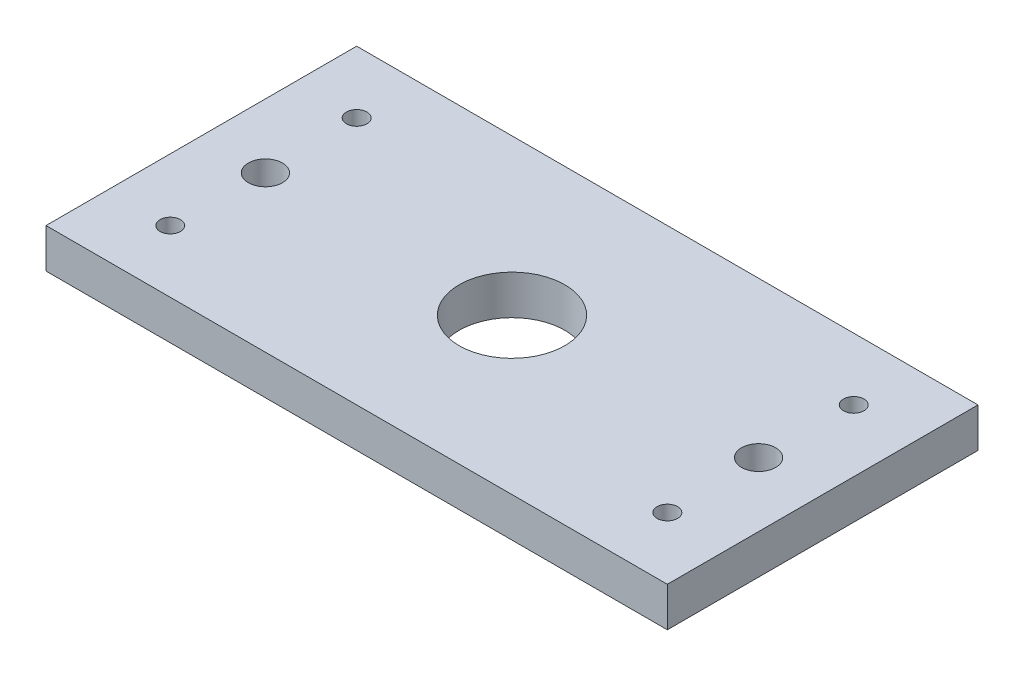
SolidWorks part; units mm, degrees
ref_plane "Front Plane" through (0, 0, 0) normal (0, 0, 1) x (1, 0, 0)
ref_plane "Top Plane" through (0, 0, 0) normal (0, 1, 0) x (1, 0, 0)
ref_plane "Right Plane" through (0, 0, 0) normal (1, 0, 0) x (0, 0, -1)
sketch "Sketch1" plane through (0, 0, 0) normal (0, 1, 0) x (1, 0, 0)
  line L0 (-50, 25) -> (50, -25) construction
  line L1 (-50, 25) -> (50, 25)
  line L2 (-50, 25) -> (-50, -25)
  line L3 (-50, -25) -> (50, -25)
  line L4 (50, 25) -> (50, -25)
  line L5 (-40, -25) -> (-40, -15) construction
  line L6 (-40, -15) -> (-50, -15) construction
  line L7 (-40, 25) -> (-40, 15) construction
  line L8 (-40, 15) -> (-50, 15) construction
  line L9 (0, -55) -> (0, 55) construction
  circle A0 centre (0, 0) radius 8.5
  circle A1 centre (-39.6875, 0) radius 2.75
  circle A3 centre (-40, 15) radius 1.65
  circle A4 centre (-40, -15) radius 1.65
  circle A5 centre (40, 15) radius 1.65
  circle A6 centre (39.6875, 0) radius 2.75
  circle A7 centre (40, -15) radius 1.65
  point P25 (-40, -2.7088)
  dimension "D1" = 17
  dimension "D2" = 5.5
  dimension "D3" = 3.3
  dimension "D4" = 10
  dimension "D5" = 100
  dimension "D6" = 50
  dimension "D7" = 79.375
extrude "Boss-Extrude1" add sketch "Sketch1" along normal blind 6.35
